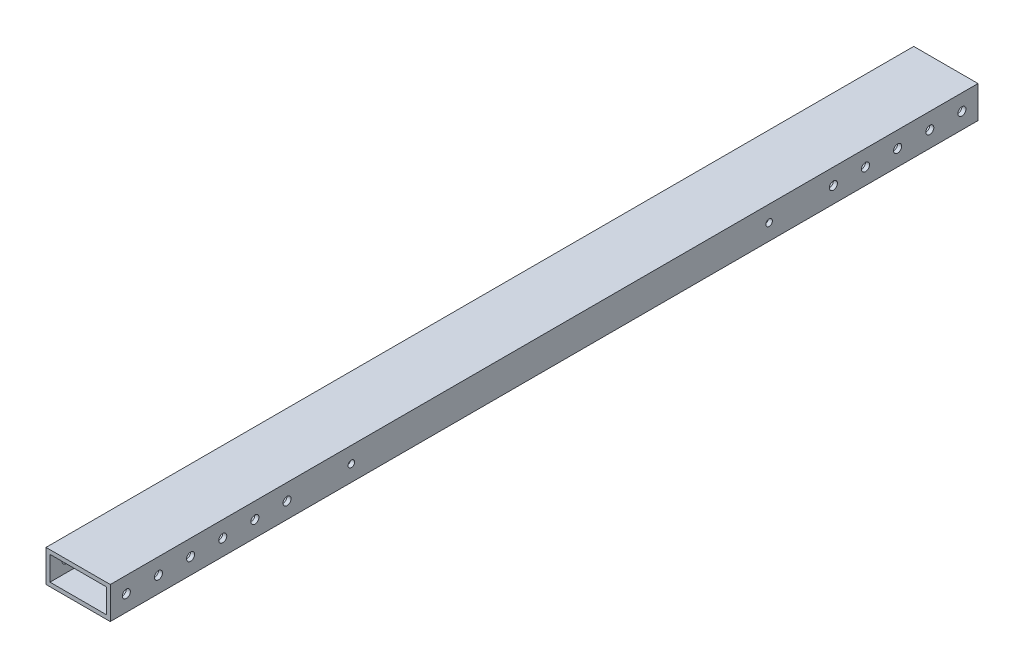
SolidWorks part; units mm, degrees
material "6061 Alloy"
ref_plane "Front Plane" through (0, 0, 0) normal (0, 0, 1) x (1, 0, 0)
ref_plane "Top Plane" through (0, 0, 0) normal (0, 1, 0) x (1, 0, 0)
ref_plane "Right Plane" through (0, 0, 0) normal (1, 0, 0) x (0, 0, -1)
sketch "Sketch1" plane through (0, 0, 0) normal (0, 0, 1) x (1, 0, 0)
  line L0 (-22.225, 9.525) -> (22.225, 9.525)
  line L2 (-25.4, 12.7) -> (25.4, 12.7)
  line L3 (-25.4, 12.7) -> (-25.4, -12.7)
  line L4 (-25.4, -12.7) -> (25.4, -12.7)
  line L5 (25.4, 12.7) -> (25.4, -12.7)
  line L10 (22.225, 9.525) -> (22.225, -9.525)
  line L11 (-22.225, -9.525) -> (22.225, -9.525)
  line L12 (-22.225, 9.525) -> (-22.225, -9.525)
  point P12 (0, 12.7)
  point P14 (25.4, 0)
  dimension "Wall Thickness" = 3.175
  dimension "Outside Width" = 50.8
  dimension "Outside Height" = 25.4
  dimension "Inside Height" = 19.05
  dimension "Inside Width" = 44.45
sketch "Sketch2" plane through (0, 0, 0) normal (1, 0, 0) x (0, 0, -1)
  line L0 (342.9, 0) -> (-342.9, 0)
  point P4 (0, 0)
  point P7 (-342.9, 0)
  point P10 (342.9, 0)
  dimension "Length" = 685.8
sketch "Sketch3" plane through (0, 0, 0) normal (0, 0, 1) x (1, 0, 0)
  line L21 (25.4, 12.7) -> (-25.4, 12.7)
  line L22 (25.4, -12.7) -> (25.4, 12.7)
  line L23 (-25.4, -12.7) -> (25.4, -12.7)
  line L24 (-25.4, 12.7) -> (-25.4, -12.7)
  line L25 (25.4, 12.7) -> (-25.4, 12.7)
  line L26 (25.4, -12.7) -> (25.4, 12.7)
  line L27 (-25.4, -12.7) -> (25.4, -12.7)
  line L28 (-25.4, 12.7) -> (-25.4, -12.7)
  line L29 (22.225, 9.525) -> (-22.225, 9.525)
  line L30 (22.225, -9.525) -> (22.225, 9.525)
  line L31 (-22.225, -9.525) -> (22.225, -9.525)
  line L32 (-22.225, 9.525) -> (-22.225, -9.525)
  line L33 (22.225, 9.525) -> (-22.225, 9.525)
  line L34 (22.225, -9.525) -> (22.225, 9.525)
  line L35 (-22.225, -9.525) -> (22.225, -9.525)
  line L36 (-22.225, 9.525) -> (-22.225, -9.525)
  dimension "D1" = 0
  dimension "D2" = 0
extrude "Boss-Extrude1" add sketch "Sketch3" along normal up to vertex (342.9 mm away) and the other way up to vertex (342.9 mm away) up to point (0, 0, 342.9) other way up to point (0, 0, -342.9)
sketch "Drawing Reference" plane through (0, 0, 0) normal (1, 0, 0) x (0, 0, -1)
  line L0 (-342.9, 0) -> (342.9, 0) construction
  line L1 (0, -12.7) -> (0, 12.7) construction
  line L2 (-342.9, -12.7) -> (342.9, -12.7) construction
  line L5 (-342.9, 12.7) -> (342.9, 12.7) construction
  point P7 (-306.324, 0)
  point P8 (306.324, 0)
  dimension "D1" = 36.576
sketch "Sketch5" plane through (25.4, 0, 0) normal (1, 0, 0) x (0, 0, -1)
  line L0 (-342.9, 0) -> (-279.4, 0)
  line L1 (-342.9, -12.7) -> (-342.9, 12.7) construction
  line L2 (-279.4, 0) -> (-254, 0)
  line L3 (-254, 0) -> (-228.6, 0)
  line L4 (-228.6, 0) -> (-203.2, 0)
sketch "Sketch8" plane through (25.4, 0, 0) normal (1, 0, 0) x (0, 0, -1)
  line L0 (342.9, 0) -> (304.8, 0)
  line L1 (342.9, -12.7) -> (342.9, 12.7) construction
  line L2 (304.8, 0) -> (279.4, 0)
  line L3 (279.4, 0) -> (254, 0)
  line L4 (254, 0) -> (228.6, 0)
  line L5 (342.9, 0) -> (330.2, 0)
hole_wizard "1/4 (0.25) Diameter Hole3" positions "Sketch12" profile "Sketch13" hole size "1/4" standard "ANSI Inch" end condition through all
sketch "Sketch12" plane through (-25.4, 0, 0) normal (-1, 0, 0) x (0, 0, 1)
  point P4 (-330.2, 0)
sketch "Sketch13" plane through (-25.4, 0, -330.2) normal (0, 1, 0) x (0, 0, 1)
  line L0 (0, 0) -> (0, 50.8)
  line L1 (0, 50.8) -> (3.175, 50.8)
  line L2 (3.175, 50.8) -> (3.175, 0)
  line L5 (3.175, 0) -> (0, 0)
  line L11 (0, -6.35) -> (0, 107.95) construction
  dimension "Thru Hole Dia." = 6.35
  dimension "Thru Hole Depth" = 50.8
hole_wizard "1/4 (0.25) Diameter Hole4" positions "Sketch14" profile "Sketch15" hole size "1/4" standard "ANSI Inch" end condition through all
sketch "Sketch14" plane through (-25.4, 0, 0) normal (-1, 0, 0) x (0, 0, 1)
  point P0 (304.8, 0)
  point P3 (330.2, 0)
sketch "Sketch15" plane through (-25.4, 0, 304.8) normal (0, 1, 0) x (0, 0, 1)
  line L0 (0, 0) -> (0, 50.8)
  line L1 (0, 50.8) -> (3.175, 50.8)
  line L2 (3.175, 50.8) -> (3.175, 0)
  line L5 (3.175, 0) -> (0, 0)
  line L11 (0, -6.35) -> (0, 107.95) construction
  dimension "Thru Hole Dia." = 6.35
  dimension "Thru Hole Depth" = 50.8
hole_wizard "1/4 (0.25) Diameter Hole5" positions "Sketch17" profile "Sketch18" hole size "1/4" standard "ANSI Inch" end condition through all
sketch "Sketch17" plane through (25.4, 0, 0) normal (1, 0, 0) x (0, 0, -1)
  point P0 (304.8, 0)
  point P3 (279.4, 0)
sketch "Sketch18" plane through (25.4, 0, -304.8) normal (0, 1, 0) x (0, 0, -1)
  line L0 (0, 0) -> (0, 50.8)
  line L1 (0, 50.8) -> (3.175, 50.8)
  line L2 (3.175, 50.8) -> (3.175, 0)
  line L5 (3.175, 0) -> (0, 0)
  line L11 (0, -6.35) -> (0, 107.95) construction
  dimension "Thru Hole Dia." = 6.35
  dimension "Thru Hole Depth" = 50.8
hole_wizard "1/4 (0.25) Diameter Hole6" positions "Sketch19" profile "Sketch20" hole size "1/4" standard "ANSI Inch" end condition through all
sketch "Sketch19" plane through (25.4, 0, 0) normal (1, 0, 0) x (0, 0, -1)
  point P0 (228.6, 0)
  point P3 (254, 0)
sketch "Sketch20" plane through (25.4, 0, -228.6) normal (0, 1, 0) x (0, 0, -1)
  line L0 (0, 0) -> (0, 50.8)
  line L1 (0, 50.8) -> (3.175, 50.8)
  line L2 (3.175, 50.8) -> (3.175, 0)
  line L5 (3.175, 0) -> (0, 0)
  line L11 (0, -6.35) -> (0, 107.95) construction
  dimension "Thru Hole Dia." = 6.35
  dimension "Thru Hole Depth" = 50.8
hole_wizard "1/4 (0.25) Diameter Hole7" positions "Sketch21" profile "Sketch22" hole size "1/4" standard "ANSI Inch" end condition through all
sketch "Sketch21" plane through (25.4, 0, 0) normal (1, 0, 0) x (0, 0, -1)
  point P0 (-203.2, 0)
  point P3 (-228.6, 0)
sketch "Sketch22" plane through (25.4, 0, 203.2) normal (0, 1, 0) x (0, 0, -1)
  line L0 (0, 0) -> (0, 50.8)
  line L1 (0, 50.8) -> (3.175, 50.8)
  line L2 (3.175, 50.8) -> (3.175, 0)
  line L5 (3.175, 0) -> (0, 0)
  line L11 (0, -6.35) -> (0, 107.95) construction
  dimension "Thru Hole Dia." = 6.35
  dimension "Thru Hole Depth" = 50.8
hole_wizard "1/4 (0.25) Diameter Hole8" positions "Sketch23" profile "Sketch24" hole size "1/4" standard "ANSI Inch" end condition through all
sketch "Sketch23" plane through (25.4, 0, 0) normal (1, 0, 0) x (0, 0, -1)
  point P0 (-279.4, 0)
  point P3 (-254, 0)
sketch "Sketch24" plane through (25.4, 0, 279.4) normal (0, 1, 0) x (0, 0, -1)
  line L0 (0, 0) -> (0, 50.8)
  line L1 (0, 50.8) -> (3.175, 50.8)
  line L2 (3.175, 50.8) -> (3.175, 0)
  line L5 (3.175, 0) -> (0, 0)
  line L11 (0, -6.35) -> (0, 107.95) construction
  dimension "Thru Hole Dia." = 6.35
  dimension "Thru Hole Depth" = 50.8
sketch "Sketch25" plane through (25.4, 0, 0) normal (1, 0, 0) x (0, 0, -1)
  line L0 (-203.2, 0) -> (-152.4, 0)
  line L1 (228.6, 0) -> (177.8, 0)
hole_wizard "13/64 (0.20313) Diameter Hole1" positions "Sketch26" profile "Sketch27" hole size "13/64" standard "ANSI Inch" end condition through all
sketch "Sketch26" plane through (25.4, 0, 0) normal (1, 0, 0) x (0, 0, -1)
  point P0 (-152.4, 0)
  point P3 (177.8, 0)
sketch "Sketch27" plane through (25.4, 0, 152.4) normal (0, 1, 0) x (0, 0, -1)
  line L0 (0, 0) -> (0, 50.8)
  line L1 (0, 50.8) -> (2.5798, 50.8)
  line L2 (2.5798, 50.8) -> (2.5798, 0)
  line L5 (2.5798, 0) -> (0, 0)
  line L11 (0, -6.35) -> (0, 107.95) construction
  dimension "Thru Hole Dia." = 5.1595
  dimension "Thru Hole Depth" = 50.8
sketch "Sketch30" plane through (-25.4, 0, 0) normal (-1, 0, 0) x (0, 0, 1)
  line L0 (203.2, 0) -> (184.15, 0)
  line L1 (203.2, 0) -> (152.4, 0) construction
  point P0 (-210.2618, 0)
hole_wizard "1/2 (0.5) Diameter Hole1" positions "Sketch33" profile "Sketch34" hole size "1/2" standard "ANSI Inch"
sketch "Sketch33" plane through (-25.4, 0, 0) normal (-1, 0, 0) x (0, 0, 1)
  point P0 (-210.2618, 0)
  point P3 (184.15, 0)
sketch "Sketch34" plane through (-25.4, 0, -210.2618) normal (0, 1, 0) x (0, 0, 1)
  line L0 (0, 0) -> (0, 10.1655)
  line L1 (0, 10.1655) -> (6.35, 6.35)
  line L2 (6.35, 6.35) -> (6.35, 0)
  line L5 (6.35, 0) -> (0, 0)
  line L10 (0, 10.1655) -> (-6.35, 6.35) construction
  line L11 (0, -6.35) -> (0, 107.95) construction
  dimension "Hole Dia." = 12.7
  dimension "Hole Depth" = 6.35
  dimension "Drill Angle" = 118
equation "\"D1@Drawing Reference\"=\"Outside Width@Sketch1\" * 0.72"
